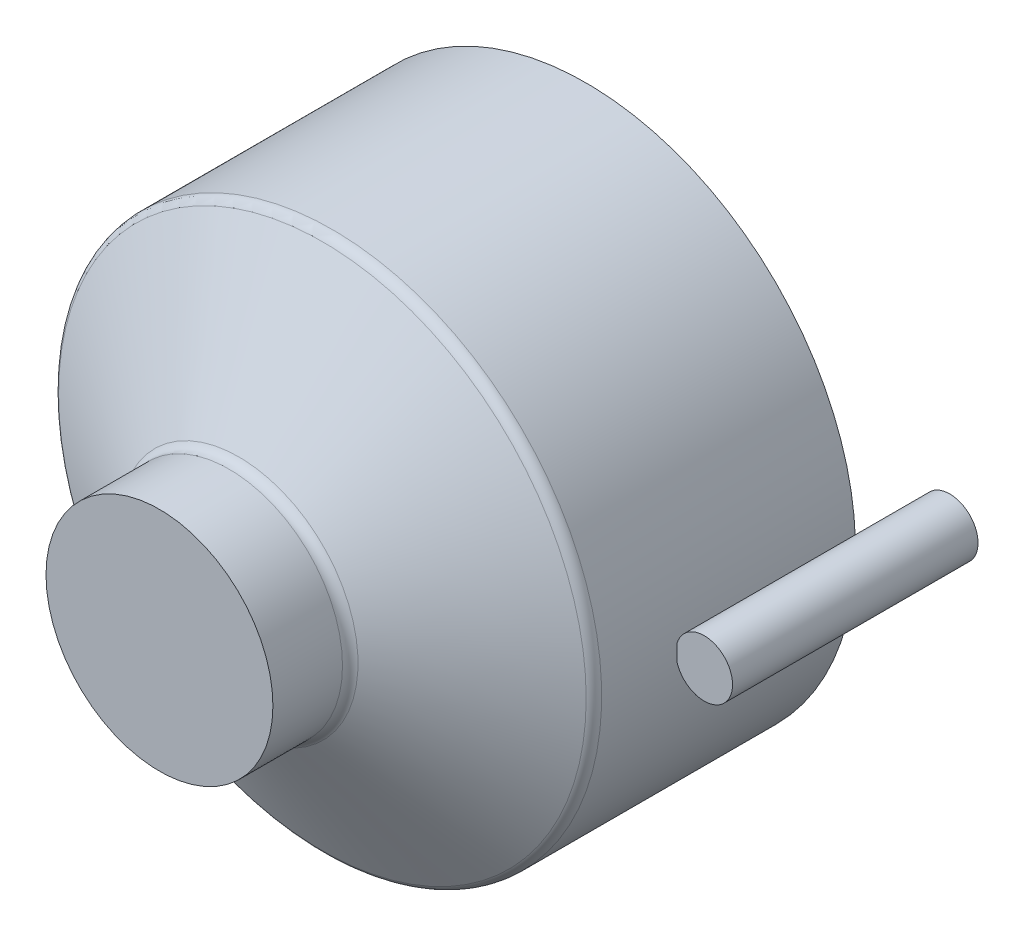
SolidWorks part; units mm, degrees
material "Custom Plastic"
ref_plane "Front Plane" through (0, 0, 0) normal (0, 0, 1) x (1, 0, 0)
ref_plane "Top Plane" through (0, 0, 0) normal (0, 1, 0) x (1, 0, 0)
ref_plane "Right Plane" through (0, 0, 0) normal (1, 0, 0) x (0, 0, -1)
sketch "Sketch2" plane through (0, 0, 0) normal (0, 1, 0) x (1, 0, 0)
  line L0 (0, 581.7739) -> (0, -735.7102) construction
  line L1 (-232.5, -44.3878) -> (-105, -118)
  line L2 (-237.5, -35.7276) -> (-237.5, 188)
  line L3 (-237.5, 188) -> (0, 188)
  line L4 (-100, -126.6603) -> (-100, -188)
  line L5 (-100, -188) -> (0, -188)
  line L6 (-237.5, -41.5011) -> (-83.1947, -41.5011) construction
  line L7 (0, 188) -> (0, -188)
  arc A0 (-105, -118) -> (-100, -126.6603) centre (-110, -126.6603) cw
  arc A1 (-232.5, -44.3878) -> (-237.5, -35.7276) centre (-227.5, -35.7276) cw
  point P11 (0, 0)
  dimension "D4" = 10
  dimension "D7" = 10
  dimension "D1" = 376
  dimension "D2" = 475
  dimension "D3" = 30
  dimension "D5" = 100
  dimension "D6" = 70
revolve "Revolve1" add sketch "Sketch2" angle 360 about L0
sketch "Sketch3" plane through (0, 0, 0) normal (0, 1, 0) x (1, 0, 0)
  line L1 (261.5, 247) -> (236.5, 247)
  line L2 (261.5, 247) -> (261.5, 30.6122)
  line L3 (261.5, 30.6122) -> (236.5, 30.6122)
  line L4 (236.5, 247) -> (236.5, 30.6122)
  line L5 (261.5, 182.65) -> (261.5, 5.5677) construction
  line L6 (-100, -188) -> (100, -188) construction
  line L7 (-232.5, -44.3878) -> (232.5, -44.3878) construction
  line L8 (237.5, -35.7276) -> (237.5, 188) construction
  dimension "D1" = 435
  dimension "D2" = 75
  dimension "D3" = 25
  dimension "D4" = 1
revolve "Revolve2" add sketch "Sketch3" angle 360 about L5
combine bodies "Combine3" operation type add bodies to combine 102 101
